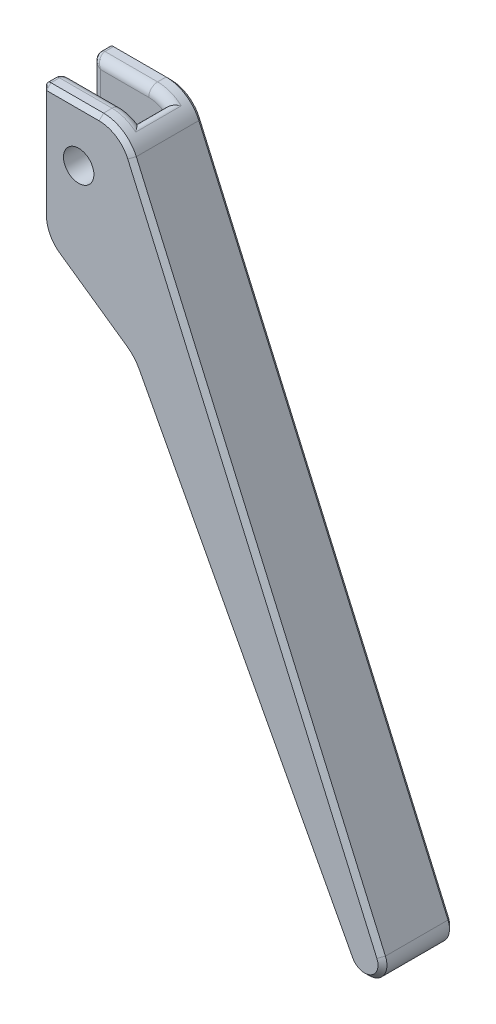
SolidWorks part; units mm, degrees
ref_plane "Front Plane" through (0, 0, 0) normal (0, 0, 1) x (1, 0, 0)
ref_plane "Top Plane" through (0, 0, 0) normal (0, 1, 0) x (1, 0, 0)
ref_plane "Right Plane" through (0, 0, 0) normal (1, 0, 0) x (0, 0, -1)
sketch "Sketch1" plane through (0, 0, 0) normal (0, 0, 1) x (1, 0, 0)
  line L0 (0, 0) -> (0, 14.7417)
  line L2 (9, 14.7417) -> (37.9315, -51.1964)
  line L4 (0, 14.7417) -> (9, 14.7417)
  line L6 (34.3327, -52.9362) -> (10, -7.0021)
  line L7 (10, -7.0021) -> (0, 0)
  line L8 (0, 0) -> (8.2, 5.7417) construction
  line L9 (8.2, 5.7417) -> (8.2, 14.7417) construction
  arc A0 (37.9315, -51.1964) -> (34.3327, -52.9362) centre (36.1, -52) cw
  circle A1 centre (4.1, 8.7417) radius 1.7
  dimension "D1" = 2
  dimension "D7" = 3.4
  dimension "D2" = 125
  dimension "D3" = 4.1
  dimension "D4" = 9
  dimension "D5" = 52
  dimension "D6" = 32
  dimension "D8" = 10
  dimension "D9" = 4.1
  dimension "D10" = 6
  dimension "D11" = 125
  dimension "D12" = 3
extrude "Boss-Extrude1" add sketch "Sketch1" along normal blind 4 and the other way blind 4
sketch "Sketch2" plane through (0, 0, 4) normal (0, 0, 1) x (1, 0, 0)
  line L0 (0, 0) -> (0, 14.7417) construction
  line L2 (8.2, 5.7417) -> (8.2, 14.7417) construction
  line L4 (0, 0) -> (8.2, 5.7417) construction
  line L5 (0, 0) -> (0, 14.7417)
  line L6 (8.2, 5.7417) -> (8.2, 14.7417)
  line L7 (0, 0) -> (8.2, 5.7417)
  line L8 (8.2, 14.7417) -> (0, 14.7417)
  circle A0 centre (4.1, 8.7417) radius 1.7 construction
  circle A1 centre (4.1, 8.7417) radius 1.7
extrude "Cut-Extrude1" cut sketch "Sketch2" against normal blind 1.55 and the other way blind 1.55 from surface contours L7 L6 L8 L5 starting at plane "Front Plane"
fillet "Fillet1" radius 2 1 edges at (8.2, 5.7417, 0)
fillet "Fillet2" radius 0.5 1 edges at (0, 0, 0) tangent propagation no
fillet "Fillet3" radius 4 1 edges at (10, -7.0021, 0)
fillet "Fillet4" radius 4 1 edges at (9, 14.7417, 0)
fillet "Fillet5" radius 4 1 edges at (0, 0, 2.775)
fillet "Fillet6" radius 0.5 3 edges at (8.2, 14.3072, 0) (0, 14.7417, -2.775) (0, 14.7417, 2.775)
fillet "Fillet8" radius 1 10 edges at (0.112, 1.1424, 1.55) (7.7998, 14.4839, 1.55) (3.4435, 14.7417, 1.55) (0.1464, 14.5953, 1.55) (7.7998, 14.4839, -1.55) (0.112, 1.1424, -1.55) (0, 8.162, -1.55) (0.1464, 14.5953, -1.55) (0, 8.162, 1.55) (3.4435, 14.7417, -1.55)
chamfer "Chamfer1" distance 0.5 angle 45 20 edges at (0.452, 0.2353, 4) (5.4582, -3.8219, 4) (0, 8.162, 4) (9.9142, -7.0778, 4) (0.1464, 14.5953, 4) (22.3919, -30.3949, 4) (3.4435, 14.7417, 4) (36.9705, -53.8006, 4) (8.5746, 14.0905, 4) (23.9907, -19.4238, 4) (0.452, 0.2353, -4) (5.4582, -3.8219, -4) (0, 8.162, -4) (9.9142, -7.0778, -4) (0.1464, 14.5953, -4) (22.3919, -30.3949, -4) (3.4435, 14.7417, -4) (36.9705, -53.8006, -4) (8.5746, 14.0905, -4) (23.9907, -19.4238, -4)
